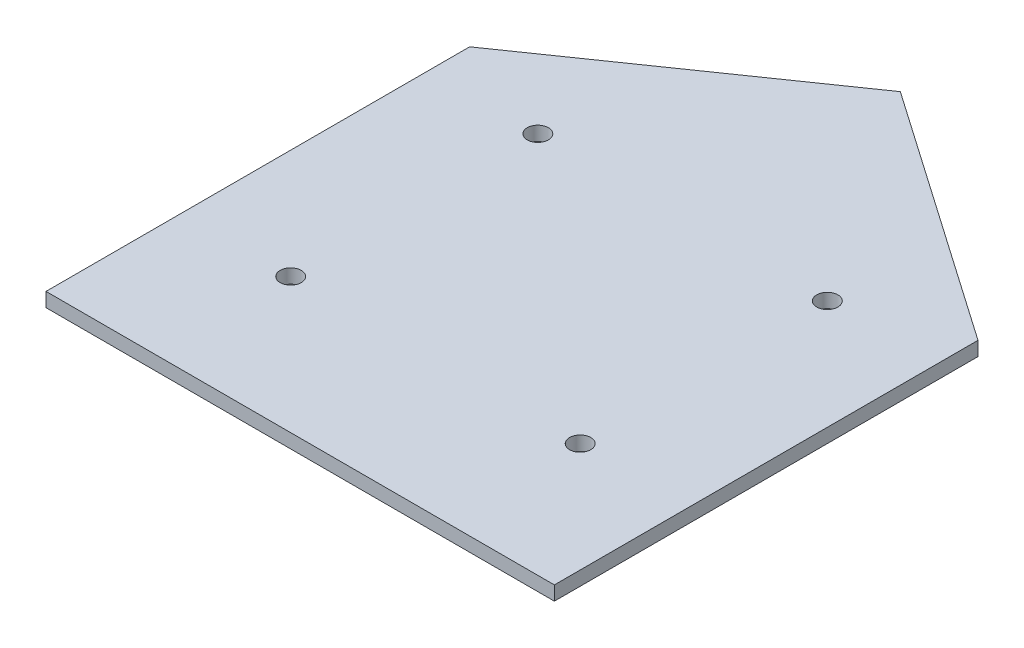
SolidWorks part; units mm, degrees
ref_plane "Front Plane" through (0, 0, 0) normal (0, 0, 1) x (1, 0, 0)
ref_plane "Top Plane" through (0, 0, 0) normal (0, 1, 0) x (1, 0, 0)
ref_plane "Right Plane" through (0, 0, 0) normal (1, 0, 0) x (0, 0, -1)
sketch "Sketch1" plane through (0, 0, 0) normal (0, 1, 0) x (1, 0, 0)
  line L0 (-36, -30) -> (-36, 30)
  line L1 (-36, -30) -> (36, -30)
  line L3 (36, -30) -> (36, 30)
  line L4 (-36, -30) -> (36, 30) construction
  line L5 (-36, 30) -> (36, -30) construction
  line L6 (-36, 30) -> (0, 55)
  line L7 (0, 55) -> (36, 30)
  circle A0 centre (-20.5, 24.1573) radius 1.5
  circle A1 centre (20.5, 24.1573) radius 1.5
  circle A2 centre (20.5, -10.8427) radius 1.5
  circle A3 centre (-20.5, -10.8427) radius 1.5
  point P1 (0, 0)
  dimension "D4" = 3
  dimension "D1" = 72
  dimension "D2" = 85
  dimension "D3" = 60
  dimension "D6" = 41
extrude "Boss-Extrude1" add sketch "Sketch1" along normal blind 2
